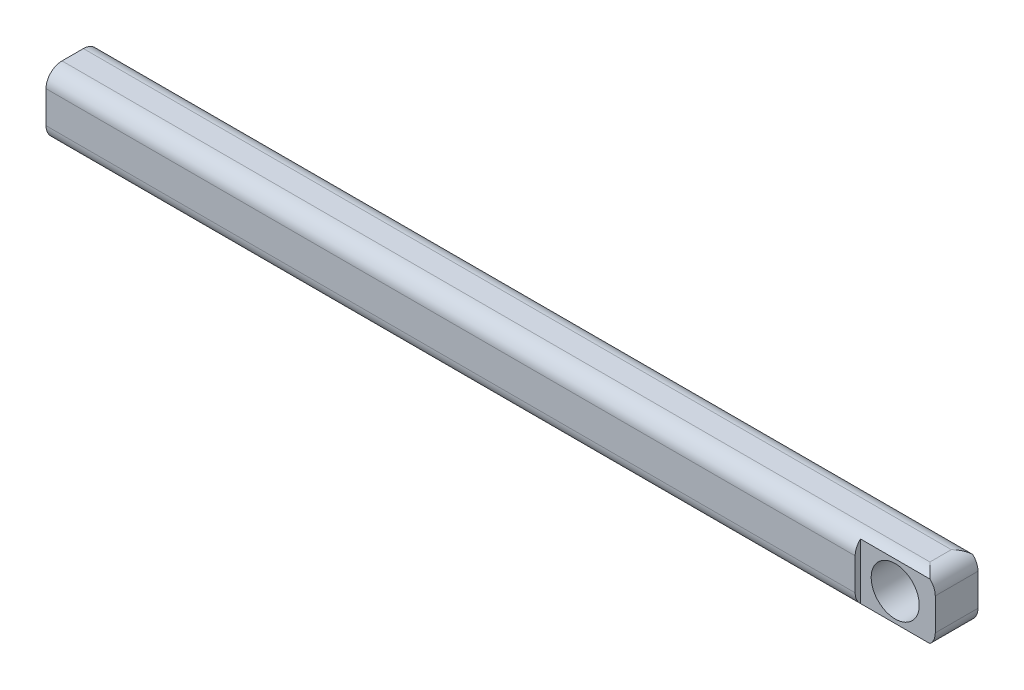
SolidWorks part; units mm, degrees
material "Acero inoxidable al cromo"
ref_plane "Front" through (0, 0, 0) normal (0, 0, 1) x (1, 0, 0)
ref_plane "Top" through (0, 0, 0) normal (0, 1, 0) x (1, 0, 0)
ref_plane "Right" through (0, 0, 0) normal (1, 0, 0) x (0, 0, -1)
sketch "Croquis1" plane through (0, 0, 0) normal (0, 0, 1) x (1, 0, 0)
  line L2 (-18.75, -15) -> (18.75, -15)
  line L3 (-18.75, -15) -> (-18.75, 15)
  line L4 (-18.75, 15) -> (18.75, 15)
  line L5 (18.75, -15) -> (18.75, 15)
  line L6 (-18.75, -15) -> (18.75, 15) construction
  line L7 (-18.75, 15) -> (18.75, -15) construction
  point P1 (0, 0)
  dimension "D1" = 37.5
  dimension "D2" = 30
extrude "Saliente-Extruir1" add sketch "Croquis1" along normal blind 15
sketch "Croquis2" plane through (0, 0, 0) normal (0, 0, 1) x (1, 0, 0)
  line L0 (-18.75, 15) -> (-18.75, -15) construction
  line L1 (-18.75, 3.7) -> (-26.75, 3.7)
  line L2 (-18.75, 3.7) -> (-18.75, -3.7)
  line L3 (-18.75, -3.7) -> (-26.75, -3.7)
  line L4 (-27.75, 2.7) -> (-27.75, -2.7)
  line L5 (0, 0) -> (-15.2309, 0) construction
  line L6 (-27.75, 0) -> (-18.75, 0) construction
  line L7 (18.75, 15) -> (-18.75, 15) construction
  line L8 (-10, 15) -> (10, 15)
  line L9 (-10, 15) -> (-10, 24)
  line L10 (-9, 25) -> (9, 25)
  line L11 (10, 15) -> (10, 24)
  line L12 (0, 0) -> (0, -15) construction
  line L13 (-18.75, -15) -> (18.75, -15) construction
  line L14 (-9, -25) -> (9, -25)
  line L15 (10, -15) -> (10, -24)
  line L16 (-10, -15) -> (10, -15)
  line L17 (-10, -15) -> (-10, -24)
  circle A0 centre (-23.25, 0) radius 2.1
  arc A1 (-26.75, -3.7) -> (-27.75, -2.7) centre (-26.75, -2.7) cw
  arc A2 (-26.75, 3.7) -> (-27.75, 2.7) centre (-26.75, 2.7) ccw
  circle A3 centre (-5.5, 20) radius 2.1
  circle A4 centre (5.5, 20) radius 2.1
  arc A5 (9, 25) -> (10, 24) centre (9, 24) cw
  arc A6 (-10, 24) -> (-9, 25) centre (-9, 24) cw
  circle A7 centre (5.5, -20) radius 2.1
  circle A8 centre (-5.5, -20) radius 2.1
  arc A9 (9, -25) -> (10, -24) centre (9, -24) ccw
  arc A10 (-10, -24) -> (-9, -25) centre (-9, -24) ccw
  point P16 (-27.75, -3.7)
  point P19 (-27.75, 3.7)
  point P35 (10, 25)
  point P38 (-10, 25)
  dimension "D2" = 4.2
  dimension "D4" = 1
  dimension "D5" = 4.2
  dimension "D6" = 11
  dimension "D9" = 1
  dimension "D10" = 5
  dimension "D1" = 7.4
  dimension "D3" = 9
  dimension "D7" = 20
  dimension "D8" = 10
extrude "Saliente-Extruir2" add sketch "Croquis2" along normal blind 1
sketch "Croquis3" plane through (18.75, 0, 0) normal (1, 0, 0) x (0, 0, -1)
  line L0 (0, 0) -> (-15, 0) construction
  line L1 (-15, -15) -> (-15, 15) construction
  line L2 (0, -15) -> (0, 15) construction
  line L3 (-10.5, -12.5) -> (-4.5, -12.5)
  line L4 (-13.5, -9.5) -> (-13.5, 9.5)
  line L5 (-10.5, 12.5) -> (-4.5, 12.5)
  line L6 (-1.5, -9.5) -> (-1.5, 9.5)
  line L7 (-13.5, -12.5) -> (-1.5, 12.5) construction
  line L8 (-13.5, 12.5) -> (-1.5, -12.5) construction
  arc A0 (-10.5, -12.5) -> (-13.5, -9.5) centre (-10.5, -9.5) cw
  arc A1 (-4.5, -12.5) -> (-1.5, -9.5) centre (-4.5, -9.5) ccw
  arc A2 (-4.5, 12.5) -> (-1.5, 9.5) centre (-4.5, 9.5) cw
  arc A3 (-13.5, 9.5) -> (-10.5, 12.5) centre (-10.5, 9.5) cw
  point P5 (-7.5, 0)
  dimension "D3" = 3
  dimension "D1" = 1.5
  dimension "D2" = 25
sketch "Croquis4" plane through (0, 0, 15) normal (0, 0, 1) x (1, 0, 0)
  line L0 (-23.25, 0) -> (64.25, 0) construction
  dimension "D1" = 87.5
extrude "Saliente-Extruir3" add sketch "Croquis3" along normal blind 35
ref_plane "Plano1" through (0, 0, 7.5) normal (0, 0, 1) x (1, 0, 0)
sketch "Croquis5" plane through (0, 0, 7.5) normal (0, 0, 1) x (1, 0, 0)
  line L14 (-23.25, 0) -> (64.25, 0) construction
  line L15 (53.75, 6) -> (71.75, 6)
  line L16 (53.75, 9.5) -> (53.75, -9.5) construction
  line L17 (71.75, 6) -> (71.75, -6)
  line L18 (71.75, -6) -> (53.75, -6)
  line L19 (53.75, -6) -> (53.75, 6)
  circle A1 centre (64.25, 0) radius 4.5
  dimension "D1" = 12
  dimension "D2" = 6
  dimension "9" = 9
  dimension "D3" = 18
extrude "Saliente-Extruir4" add sketch "Croquis5" along normal mid plane 10
sketch "Croquis6" plane through (71.75, 0, 0) normal (1, 0, 0) x (0, 0, -1)
  line L0 (-11.5, 6) -> (-11.5, -6)
  line L1 (-12.5, 6) -> (-2.5, 6) construction
  line L2 (-12.5, -6) -> (-2.5, -6) construction
  line L3 (-3.5, 6) -> (-3.5, -6)
  line L4 (-12.5, 6) -> (-2.5, 6) construction
  line L5 (-12.5, -6) -> (-2.5, -6) construction
  line L6 (-12.5, -6) -> (-12.5, 6) construction
  line L7 (-2.5, -6) -> (-2.5, 6) construction
  line L8 (-3.5, -6) -> (-2.5, -6)
  line L9 (-11.5, 6) -> (-12.5, 6)
  line L12 (-2.5, -6) -> (-2.5, 6)
  line L13 (-2.5, 6) -> (-12.5, 6)
  line L14 (-12.5, 6) -> (-12.5, -6)
  line L15 (-12.5, -6) -> (-2.5, -6)
  line L16 (-2.5, -6) -> (-2.5, 6)
  line L17 (-2.5, 6) -> (-3.5, 6)
  line L18 (-12.5, 6) -> (-12.5, -6)
  line L19 (-12.5, -6) -> (-11.5, -6)
  dimension "D1" = 1
  dimension "D2" = 1
  dimension "D3" = 0
extrude "Cortar-Extruir2" cut sketch "Croquis6" against normal blind 14
fillet "Redondeo1" radius 3 2 edges at (71.75, -6, 7.5) (71.75, 6, 7.5)
fillet "Redondeo2" radius 3 4 edges at (55.75, -6, 12.5) (55.75, -6, 2.5) (55.75, 6, 2.5) (55.75, 6, 12.5)
sketch "Croquis7" plane through (0, 0, 15) normal (0, 0, 1) x (1, 0, 0)
  line L0 (53.75, 3) -> (53.75, -3) construction
  line L1 (53.75, 15) -> (77.9133, 15)
  line L2 (53.75, 15) -> (53.75, -21.2112)
  line L3 (53.75, -21.2112) -> (77.9133, -21.2112)
  line L4 (77.9133, 15) -> (77.9133, -21.2112)
extrude "Cortar-Extruir3" cut sketch "Croquis7" against normal through all and the other way through all flip side to cut
sketch "Croquis10" plane through (53.75, 0, 0) normal (-1, 0, 0) x (0, 0, 1)
  line L4 (5.5, -6) -> (9.5, -6)
  line L5 (12.5, -3) -> (12.5, 3)
  line L6 (9.5, 6) -> (5.5, 6)
  line L7 (2.5, 3) -> (2.5, -3)
  line L8 (5.5, -6) -> (9.5, -6)
  line L9 (12.5, -3) -> (12.5, 3)
  line L10 (9.5, 6) -> (5.5, 6)
  line L11 (2.5, 3) -> (2.5, -3)
  arc A4 (9.5, -6) -> (12.5, -3) centre (9.5, -3) ccw
  arc A5 (12.5, 3) -> (9.5, 6) centre (9.5, 3) ccw
  arc A6 (5.5, 6) -> (2.5, 3) centre (5.5, 3) ccw
  arc A7 (2.5, -3) -> (5.5, -6) centre (5.5, -3) ccw
  arc A8 (9.5, -6) -> (12.5, -3) centre (9.5, -3) ccw
  arc A9 (12.5, 3) -> (9.5, 6) centre (9.5, 3) ccw
  arc A10 (5.5, 6) -> (2.5, 3) centre (5.5, 3) ccw
  arc A11 (2.5, -3) -> (5.5, -6) centre (5.5, -3) ccw
  dimension "D1" = 0
extrude "Saliente-Extruir5" add sketch "Croquis10" along normal blind 147.5
sketch "Croquis11" plane through (-93.75, 0, 0) normal (-1, 0, 0) x (0, 0, 1)
  line L4 (5.5, -6) -> (9.5, -6)
  line L5 (12.5, -3) -> (12.5, 3)
  line L6 (9.5, 6) -> (5.5, 6)
  line L7 (2.5, 3) -> (2.5, -3)
  line L8 (5.5, -6) -> (9.5, -6)
  line L9 (12.5, -3) -> (12.5, 3)
  line L10 (9.5, 6) -> (5.5, 6)
  line L11 (2.5, 3) -> (2.5, -3)
  arc A4 (2.5, -3) -> (5.5, -6) centre (5.5, -3) ccw
  arc A5 (9.5, -6) -> (12.5, -3) centre (9.5, -3) ccw
  arc A6 (12.5, 3) -> (9.5, 6) centre (9.5, 3) ccw
  arc A7 (5.5, 6) -> (2.5, 3) centre (5.5, 3) ccw
  arc A8 (2.5, -3) -> (5.5, -6) centre (5.5, -3) ccw
  arc A9 (9.5, -6) -> (12.5, -3) centre (9.5, -3) ccw
  arc A10 (12.5, 3) -> (9.5, 6) centre (9.5, 3) ccw
  arc A11 (5.5, 6) -> (2.5, 3) centre (5.5, 3) ccw
  point P0 (7.5, -6)
  dimension "D4" = 3
  dimension "D2" = 12
  dimension "D3" = 10
  dimension "D1" = 0
